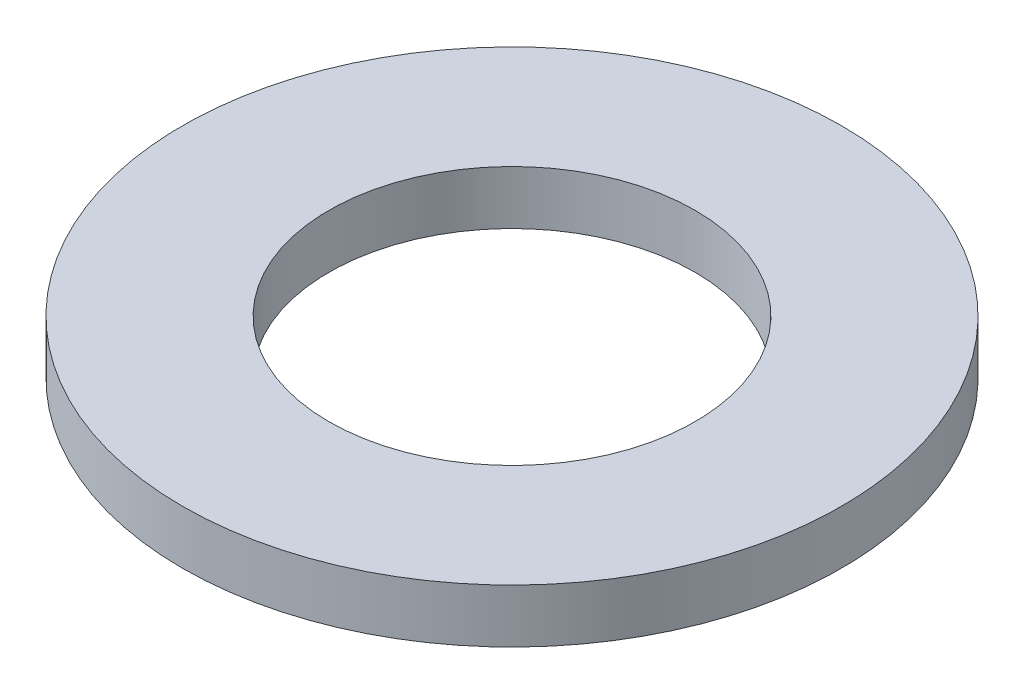
SolidWorks part; units mm, degrees
ref_plane "Front Plane" through (0, 0, 0) normal (0, 0, 1) x (1, 0, 0)
ref_plane "Top Plane" through (0, 0, 0) normal (0, 1, 0) x (1, 0, 0)
ref_plane "Right Plane" through (0, 0, 0) normal (1, 0, 0) x (0, 0, -1)
sketch "Sketch1" plane through (0, 0, 0) normal (0, 1, 0) x (1, 0, 0)
  circle A0 centre (0, 0) radius 67.5
  dimension "FLANGE_OD" = 135
extrude "Boss-Extrude1" add sketch "Sketch1" along normal blind 11
sketch "Sketch2" plane through (0, 0, 0) normal (0, 1, 0) x (1, 0, 0)
  circle A0 centre (0, 0) radius 37.5
  dimension "BORE_D" = 75
extrude "Cut-Extrude1" cut sketch "Sketch2" along normal through all
sketch "Sketch3" plane through (0, 11, 0) normal (0, 1, 0) x (1, 0, 0)
  circle A0 centre (0, 0) radius 26.2322 construction
  circle A1 centre (-26.2322, 0) radius 1.7228
  dimension "BOLT_D" = 3.4457
  dimension "BOLT_PCD" = 52.4645
extrude "Cut-Extrude2" cut sketch "Sketch3" against normal blind 8.3026 rebuild error yes
pattern_circular "CirPattern1" count 4 over 360 rebuild error yes
